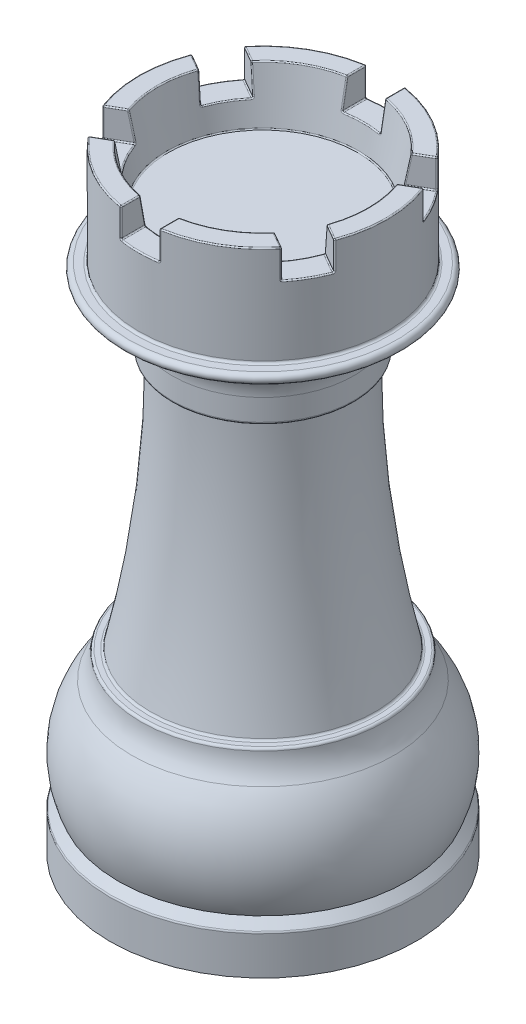
SolidWorks part; units mm, degrees
ref_plane "Front Plane" through (0, 0, 0) normal (0, 0, 1) x (1, 0, 0)
ref_plane "Top Plane" through (0, 0, 0) normal (0, 1, 0) x (1, 0, 0)
ref_plane "Right Plane" through (0, 0, 0) normal (1, 0, 0) x (0, 0, -1)
sketch "Sketch1" plane through (0, 0, 0) normal (0, 0, 1) x (1, 0, 0)
  line L0 (16, 4) -> (16, 0)
  line L1 (15.1036, 5) -> (15.9268, 4.1768)
  line L2 (9.5, 48) -> (9.5, 45.75)
  line L3 (13, 64) -> (13, 53.7813)
  line L4 (10.0302, 58.5) -> (0, 58.5)
  line L5 (13, 64) -> (11, 64)
  line L6 (14.0312, 53.5313) -> (13.25, 53.5313)
  line L7 (9.25, 45.5) -> (9, 45.5)
  line L8 (11, 64) -> (10.0302, 58.5)
  line L9 (16, 0) -> (0, 0)
  line L10 (12.5, 18.5) -> (12, 18.5)
  line L11 (0, 0) -> (0, 58.5)
  line L12 (0, 0) -> (0, -4.8979) construction
  arc A0 (16, 4) -> (15.9268, 4.1768) centre (15.75, 4) ccw
  arc A1 (15.1036, 5) -> (13.7193, 15.7192) centre (5.6068, 9.2226) ccw
  arc A2 (12.7496, 18.2633) -> (13.7193, 15.7192) centre (17.1905, 18.4991) ccw
  arc A3 (12.7496, 18.2633) -> (12.5, 18.5) centre (12.5, 18.25) ccw
  arc A4 (8.75, 45.2509) -> (11.7565, 18.6933) centre (124, 44.849) ccw
  arc A5 (9, 45.5) -> (8.75, 45.2509) centre (9, 45.25) ccw
  arc A6 (9.25, 45.5) -> (9.5, 45.75) centre (9.25, 45.75) ccw
  arc A7 (14.0312, 52.5312) -> (9.5, 48) centre (14.0312, 48) ccw
  arc A8 (14.0312, 52.5312) -> (14.0312, 53.5313) centre (14.0312, 53.0312) ccw
  arc A9 (13, 53.7813) -> (13.25, 53.5313) centre (13.25, 53.7813) ccw
  arc A10 (11.7565, 18.6933) -> (12, 18.5) centre (12, 18.75) ccw
  dimension "D3" = 0.25
  dimension "D4" = 5
  dimension "D5" = 4.4471
  dimension "D6" = 12
  dimension "D7" = 4.5312
  dimension "D8" = 0.5
  dimension "D9" = 0.25
  dimension "D10" = 10.3932
  dimension "D12" = 18.5
  dimension "D16" = 9.5
  dimension "D1" = 32
  dimension "D2" = 64
  dimension "D11" = 135
  dimension "D13" = 12.5
  dimension "D14" = 45.5
  dimension "D15" = 9
  dimension "D17" = 124
  dimension "D18" = 13
  dimension "D19" = 10
  dimension "D20" = 2
  dimension "D21" = 4
  dimension "D24" = 48
  dimension "D25" = 58.5
revolve "Revolve1" add sketch "Sketch1" angle 360 about L12
sketch "Sketch2" plane through (0, 64, 0) normal (0, 1, 0) x (1, 0, 0)
  line L0 (13.4647, 5.4644) -> (-11.4647, -8.9285)
  line L1 (-2, 14.393) -> (2, 14.393)
  line L2 (-2, 14.393) -> (-2, -14.393)
  line L3 (-2, -14.393) -> (2, -14.393)
  line L4 (2, 14.393) -> (2, -14.393)
  line L5 (-2, 14.393) -> (2, -14.393) construction
  line L6 (-2, -14.393) -> (2, 14.393) construction
  line L7 (11.4647, 8.9285) -> (13.4647, 5.4644)
  line L8 (11.4647, 8.9285) -> (-13.4647, -5.4644)
  line L9 (-13.4647, -5.4644) -> (-11.4647, -8.9285)
  line L10 (11.4647, -8.9285) -> (-13.4647, 5.4644)
  line L11 (13.4647, -5.4644) -> (11.4647, -8.9285)
  line L12 (13.4647, -5.4644) -> (-11.4647, 8.9285)
  line L13 (-11.4647, 8.9285) -> (-13.4647, 5.4644)
  line L14 (-2, -14.393) -> (-2, 14.393)
  line L15 (2, -14.393) -> (-2, -14.393)
  line L16 (2, -14.393) -> (2, 14.393)
  line L17 (2, 14.393) -> (-2, 14.393)
  line L18 (-13.4647, -5.4644) -> (11.4647, 8.9285)
  line L19 (-11.4647, -8.9285) -> (-13.4647, -5.4644)
  line L20 (-11.4647, -8.9285) -> (13.4647, 5.4644)
  line L21 (13.4647, 5.4644) -> (11.4647, 8.9285)
  line L22 (-11.4647, 8.9285) -> (13.4647, -5.4644)
  line L23 (-13.4647, 5.4644) -> (-11.4647, 8.9285)
  line L24 (-13.4647, 5.4644) -> (11.4647, -8.9285)
  line L25 (11.4647, -8.9285) -> (13.4647, -5.4644)
  circle A0 centre (0, 0) radius 14.5313 construction
  circle A1 centre (0, 0) radius 11 construction
  point P0 (0, 0)
  circle M2 centre (0, 0) radius 11
  circle M3 centre (0, 0) radius 13
  dimension "D2" = 6
extrude "Cut-Extrude3" cut sketch "Sketch2" against normal blind 3 contours L12 L10 M2 M3 | L2 L12 L10 L8 M2 | L12 L13 L10 M3 | L12 L0 L8 L4 M2 | L12 L0 L4 L10 M2 | L2 L10 L8 L0 M2 | L12 L10 M3 M2 | L11 L12 L10 M3 | L8 L0 M3 M2 | L7 L8 L0 M3 | L8 L0 M2 M3 | L8 L9 L0 M3 | L4 L10 L0 L2 M2 | L4 L2 M2 M3 | L4 L2 L3 M3 | L4 L1 L2 M3 | L4 L2 M3 M2 | L12 L8 L4 L2 M2 | L8 L12 L2 | L12 L4 L8 | L4 L12 L8 L2 L10 L0 | L10 L2 L8 | L10 L4 L0 | L0 L12 L4 | L0 L10 L2 | L4 L3 L2 L1 region at (11.8386, 64, -6.835) region at (10.3435, 64, -5.9718) region at (5.981, 64, -3.4531) region at (5.981, 64, 3.4531) region at (2.6667, 64, 0) region at (10.3435, 64, 5.9718) region at (11.8386, 64, 6.835) region at (0, 64, -13.67) region at (0, 64, -11.9436) region at (1.3333, 64, 2.3094) region at (0, 64, 0) region at (1.3333, 64, -2.3094) region at (0, 64, -6.9062) region at (0, 64, 6.9062) region at (-1.3333, 64, 2.3094) region at (-1.3333, 64, -2.3094) region at (0, 64, 11.9436) region at (0, 64, 13.67) region at (-11.8386, 64, -6.835) region at (-10.3435, 64, -5.9718) region at (-5.981, 64, 3.4531) region at (-2.6667, 64, 0) region at (-5.981, 64, -3.4531) region at (-10.3435, 64, 5.9718) region at (-11.8386, 64, 6.835)
fillet "Fillet1" radius 0.125 73 edges at (12.1243, 62.5, -4.6906) (10.1243, 62.5, -8.1547) (2, 62.5, -12.8452) (-2, 62.5, -12.8452) (-10.1243, 62.5, -8.1547) (-12.1243, 62.5, -4.6906) (-12.1243, 62.5, 4.6906) (-10.1243, 62.5, 8.1547) (-2, 62.5, 12.8452) (2, 62.5, 12.8452) (10.1243, 62.5, 8.1547) (12.1243, 62.5, 4.6906) (6.5, 64, -11.2583) (9.2459, 64, -7.6475) (2, 64, -11.8309) (-9.2459, 64, -7.6475) (-6.5, 64, -11.2583) (-2, 64, -11.8309) (-11.2459, 64, -4.1834) (-11.2459, 64, 4.1834) (-13, 64, 0) (-9.2459, 64, 7.6475) (-2, 64, 11.8309) (-6.5, 64, 11.2583) (9.2459, 64, 7.6475) (6.5, 64, 11.2583) (2, 64, 11.8309) (13, 64, 0) (11.2459, 64, 4.1834) (11.2459, 64, -4.1834) (11.0128, 61, -4.0488) (9.0128, 61, -7.5129) (11.2583, 61, -6.5) (2, 61, -11.5617) (-2, 61, -11.5617) (0, 61, -13) (-9.0128, 61, -7.5129) (-11.0128, 61, -4.0488) (-11.2583, 61, -6.5) (-11.0128, 61, 4.0488) (-9.0128, 61, 7.5129) (-11.2583, 61, 6.5) (-2, 61, 11.5617) (2, 61, 11.5617) (0, 61, 13) (9.0128, 61, 7.5129) (11.0128, 61, 4.0488) (11.2583, 61, 6.5) (-9.0682, 61, 5.2355) (-11, 64, 0) (-9.0682, 61, -5.2355) (-5.5, 64, -9.5263) (0, 61, -10.471) (5.5, 64, -9.5263) (9.0682, 61, -5.2355) (11, 64, 0) (9.0682, 61, 5.2355) (5.5, 64, 9.5263) (0, 61, 10.471) (-5.5, 64, 9.5263) (0, 58.5, 10.0302)
scale "Scale1" scale about origin uniform scaling yes scale factor 0.71875
sketch "Sketch3" plane through (0, 0, 0) normal (0, -1, 0) x (1, 0, 0)
  circle A0 centre (0, 0) radius 10.2
  dimension "D1" = 20.4
extrude "Cut-Extrude4" cut sketch "Sketch3" against normal blind 9
sketch "Sketch4" plane through (0, 9, 0) normal (0, -1, 0) x (1, 0, 0)
  circle A0 centre (0, 0) radius 4.4
  dimension "D1" = 8.8
extrude "Cut-Extrude5" [suppressed] cut sketch "Sketch4" against normal blind 5
sketch "Sketch5" [suppressed] plane through (0, 13, 0) normal (0, -1, 0) x (1, 0, 0)
  circle A0 centre (0, 0) radius 2.2
  dimension "D1" = 4.4
extrude "Cut-Extrude6" [suppressed] cut sketch "Sketch5" against normal blind 13
sketch "Sketch6" plane through (0, 0, 0) normal (0, 0, 1) x (1, 0, 0)
  line L0 (-10.75, 1) -> (0, 1)
  line L1 (-10.75, 1) -> (-10.75, 0)
  line L2 (-10.75, 0) -> (0, 0)
  line L3 (0, 0) -> (0, -1) construction
  line L4 (0, 0) -> (0, 1)
  dimension "D2" = 1
  dimension "D4" = 21.5
revolve "Cut-Revolve1" cut sketch "Sketch6" angle 360 about L3
sketch "Sketch7" plane through (0, 0, 0) normal (0, 0, 1) x (1, 0, 0)
  line L0 (0, 0) -> (-10.55, 0)
  line L1 (0, 0) -> (0, 1)
  line L2 (0, 1) -> (-10.55, 1)
  line L3 (-10.55, 0) -> (-10.55, 1)
  line L4 (0, 0) -> (0, -1.3413) construction
  line L5 (-10.75, 1) -> (10.75, 1) construction
  line L6 (0, 1) -> (0, 2)
  line L7 (0, 2) -> (-10, 2)
  line L8 (-10, 2) -> (-10, 1)
  dimension "D1" = 21.1
  dimension "D2" = 20
  dimension "D3" = 2
revolve "Base (Black Rook)" [suppressed] add sketch "Sketch7" angle 360 about L4
sketch "Sketch8" plane through (0, 0, 0) normal (0, 0, 1) x (1, 0, 0)
  line L0 (-10.2, 1) -> (10.2, 1) construction
  line L3 (0, 1) -> (-10.55, 1) construction
  line L4 (-10.55, 0) -> (-10.55, 1) construction
  line L5 (0, 0) -> (-10.55, 0) construction
  line L6 (0, 0) -> (0, 1) construction
  line L7 (0, 1) -> (0, 2.5)
  line L8 (0, 2.5) -> (-10, 2.5)
  line L9 (-10, 2.5) -> (-10, 1)
  line L10 (0, 1) -> (-10.55, 1)
  line L11 (-10.55, 0) -> (-10.55, 1)
  line L12 (0, 0) -> (-10.55, 0)
  line L13 (0, 0) -> (0, 1)
  line L14 (0, 0) -> (0, -0.8353) construction
  dimension "D1" = 20
  dimension "D3" = 2.5
revolve "Base (White Rook)" add sketch "Sketch8" angle 360 about L14 region at (-5, 1.75, 0) region at (-5.275, 0.5, 0)
equation "\"D1@Cut-Extrude5\"=\"SocketDepth\""
equation "\"D1@Sketch3\"=\"BaseOuterDiam\"+0.4"
equation "\"D1@Cut-Extrude4\"=6mm+3mm"
equation "\"D1@Cut-Extrude2\"=\"SocketDepth\""
equation "\"D1@Sketch4\"=\"SocketDiam\"+0.3"
equation "\"D1@Cut-Extrude3\"=3"
equation "\"D1@Cut-Extrude1\"=\"PawnHeight\"+\"MagThickness\"-\"FeltThickness\""
equation "\"D1@Sketch2\"=4"
equation "\"PawnHeight\"= 1mm"
equation "\"MagDiam\"= 12mm"
equation "\"MagThickness\"= 3mm"
equation "\"KnightHeight\"= 2.5mm"
equation "\"RookHeight\"= 4mm"
equation "\"BishopHeight\"= 5.5mm"
equation "\"QueenHeight\"= 6.5mm"
equation "\"KingHeight\"= 8mm"
equation "\"WeightOuterDiam\"= 18mm"
equation "\"WeightInnerDiam\"= \"MagDiam\" + 0.3mm"
equation "\"WeightHeight\"= 9mm"
equation "\"BaseOuterDiam\"= 20mm"
equation "\"BaseInnerDiam\"= 12.7mm"
equation "\"FeltThickness\"= 1mm"
equation "\"ThreadedDepth\"= 10mm"
equation "\"TapdrillDiam\"= 4.4mm"
equation "\"SocketDepth\"= 5mm"
equation "\"SocketDiam\"= 8.5mm"
equation "\"D1@Sketch6\"=\"SocketDiam\"+0.3"
equation "\"D1@Sketch7\"=21.1mm"
equation "\"D1@Sketch5\"=\"TapdrillDiam\""
equation "\"D1@Cut-Extrude6\"=\"ThreadedDepth\"+3mm"
